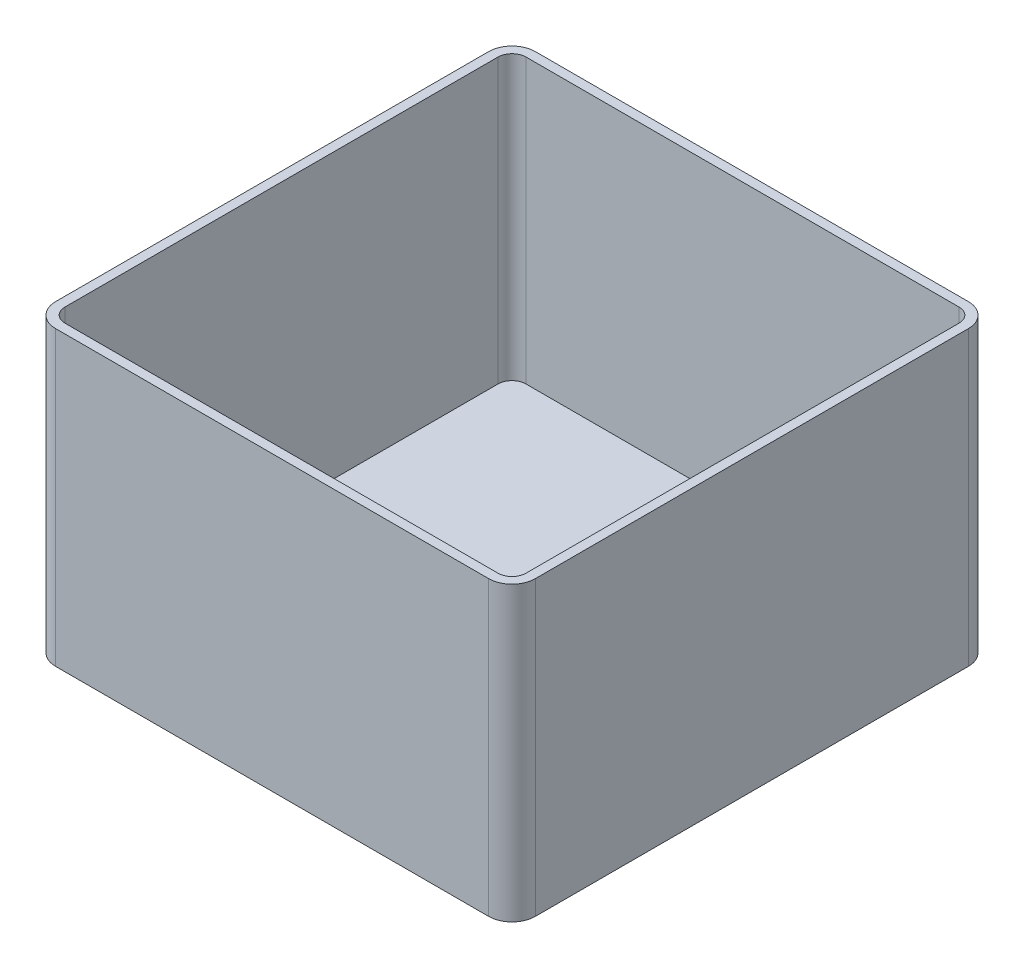
SolidWorks part; units mm, degrees
ref_plane "Front Plane" through (0, 0, 0) normal (0, 0, 1) x (1, 0, 0)
ref_plane "Top Plane" through (0, 0, 0) normal (0, 1, 0) x (1, 0, 0)
ref_plane "Right Plane" through (0, 0, 0) normal (1, 0, 0) x (0, 0, -1)
sketch "Sketch1" plane through (0, 0, 0) normal (0, 1, 0) x (1, 0, 0)
  line L0 (-26.035, 26.035) -> (26.035, -26.035) construction
  line L1 (-26.035, 26.035) -> (26.035, 26.035)
  line L2 (-26.035, 26.035) -> (-26.035, -26.035)
  line L3 (-26.035, -26.035) -> (26.035, -26.035)
  line L4 (26.035, 26.035) -> (26.035, -26.035)
  dimension "D1" = 52.07
extrude "Boss-Extrude1" add sketch "Sketch1" along normal blind 31.75
fillet "Fillet1" radius 2.54 4 edges at (-26.035, 15.875, -26.035) (-26.035, 15.875, 26.035) (26.035, 15.875, 26.035) (26.035, 15.875, -26.035)
shell "Shell2" thickness 1.016 removed face at (0, 31.75, 0)
